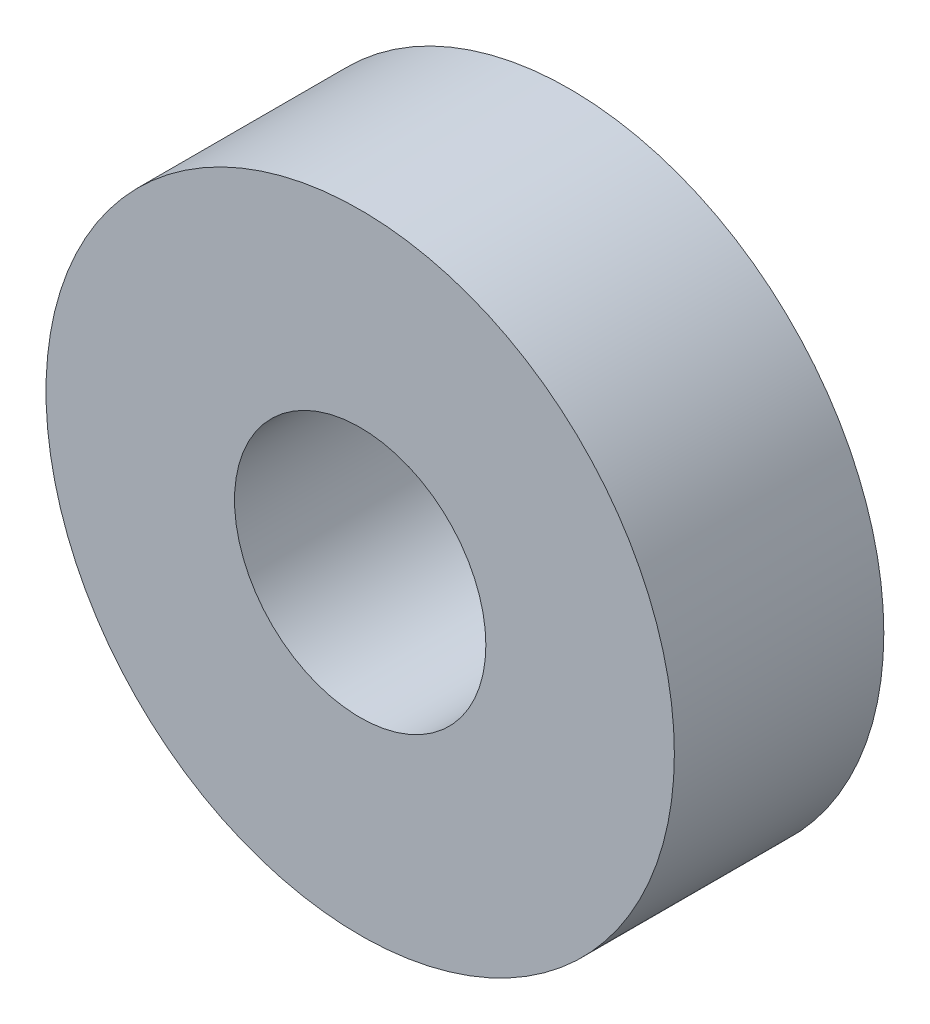
SolidWorks part; units mm, degrees
ref_plane "前视基准面" through (0, 0, 0) normal (0, 0, 1) x (1, 0, 0)
ref_plane "上视基准面" through (0, 0, 0) normal (0, 1, 0) x (1, 0, 0)
ref_plane "右视基准面" through (0, 0, 0) normal (1, 0, 0) x (0, 0, -1)
sketch "草图1" plane through (0, 0, 0) normal (0, 0, 1) x (1, 0, 0)
  circle A0 centre (0, 0) radius 7.5
  circle A1 centre (0, 0) radius 3
  dimension "D1" = 15
  dimension "D2" = 6
extrude "凸台-拉伸1" add sketch "草图1" along normal blind 2.5 and the other way blind 2.5
